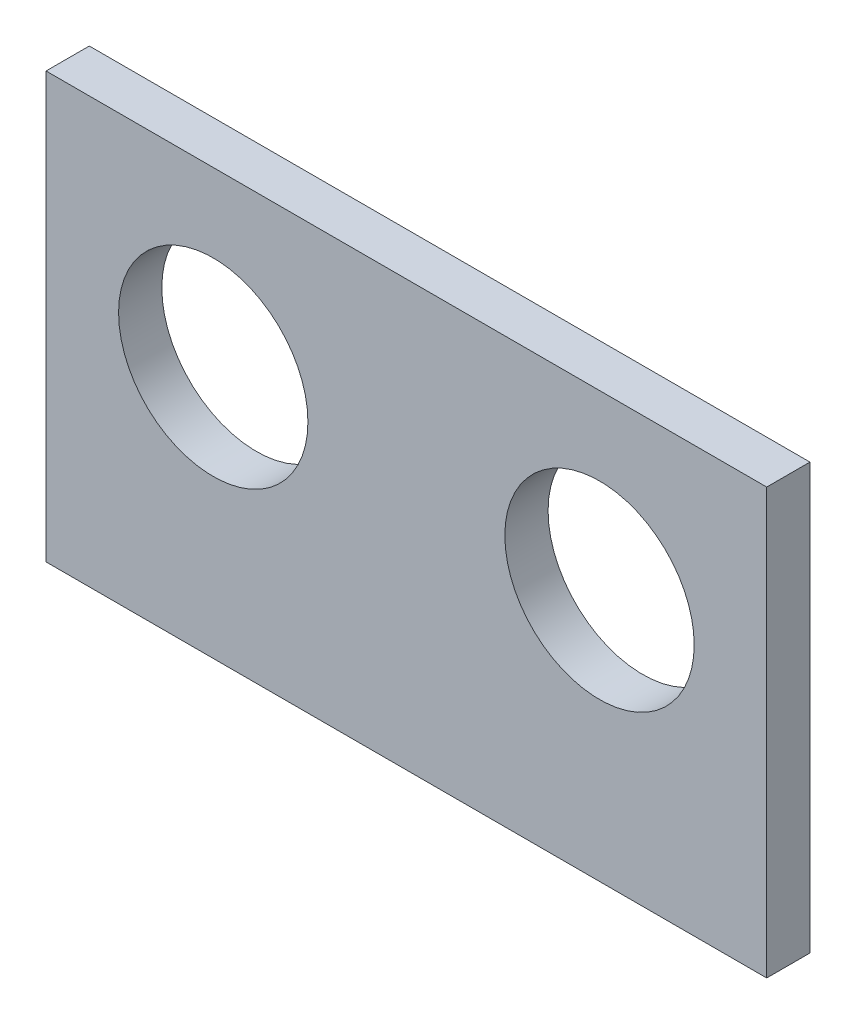
SolidWorks part; units mm, degrees
ref_plane "Front Plane" through (0, 0, 0) normal (0, 0, 1) x (1, 0, 0)
ref_plane "Top Plane" through (0, 0, 0) normal (0, 1, 0) x (1, 0, 0)
ref_plane "Right Plane" through (0, 0, 0) normal (1, 0, 0) x (0, 0, -1)
sketch "Sketch1" plane through (0, 0, 0) normal (0, 0, 1) x (1, 0, 0)
  line L0 (-6.7, 1.375) -> (6.7, 1.375) construction
  line L1 (-12.5, -7.375) -> (12.5, -7.375)
  line L2 (-12.5, -7.375) -> (-12.5, 7.375)
  line L3 (-12.5, 7.375) -> (12.5, 7.375)
  line L4 (12.5, -7.375) -> (12.5, 7.375)
  line L5 (-12.5, -7.375) -> (12.5, 7.375) construction
  line L6 (-12.5, 7.375) -> (12.5, -7.375) construction
  line L7 (-12.5, 1.375) -> (12.5, 1.375) construction
  line L8 (-6.7, -4.875) -> (-6.7, -7.375) construction
  line L9 (0, 7.375) -> (0, -7.375) construction
  circle A0 centre (-6.7, 1.375) radius 6.25
  circle A1 centre (6.7, 1.375) radius 6.25
  point P4 (0, 0)
  point P6 (0, 0)
  point P12 (0, 0)
  point P18 (0, 1.375)
  dimension "D1" = 12.5
  dimension "D2" = 13.4
  dimension "D3" = 6
  dimension "D4" = 25
  dimension "D5" = 2.5
extrude "Boss-Extrude1" add sketch "Sketch1" along normal blind 1.5 contours L3 A1 A0 L2 L1 L4 | L3 A0 | A1 L4 L3 | A0 L3 L2 | L3 A1 L4 region at (0, -3.3295, 0) region at (-6.6303, 1.3454, 0) region at (6.6303, 1.3454, 0) region at (-11.3788, 6.3435, 0) region at (11.3788, 6.3435, 0)
sketch "Sketch2" plane through (0, 0, 1.5) normal (0, 0, 1) x (1, 0, 0)
  line L1 (-9.09, -5.265) -> (9.09, -5.265) construction
  line L2 (-9.09, -5.265) -> (-9.09, -6.935) construction
  line L3 (-9.09, -6.935) -> (9.09, -6.935) construction
  line L4 (9.09, -5.265) -> (9.09, -6.935) construction
  line L5 (-9.09, -5.265) -> (9.09, -6.935) construction
  line L6 (-9.09, -6.935) -> (9.09, -5.265) construction
  point P4 (0, -6.1)
sketch "Sketch3" plane through (0, 0, 0) normal (0, 0, -1) x (-1, 0, 0)
  circle A0 centre (-6.7, 1.375) radius 3.2843
  circle A1 centre (6.7, 1.375) radius 3.2843
  dimension "D1" = 6.5686
extrude "Cut-Extrude1" cut sketch "Sketch3" against normal blind 10
